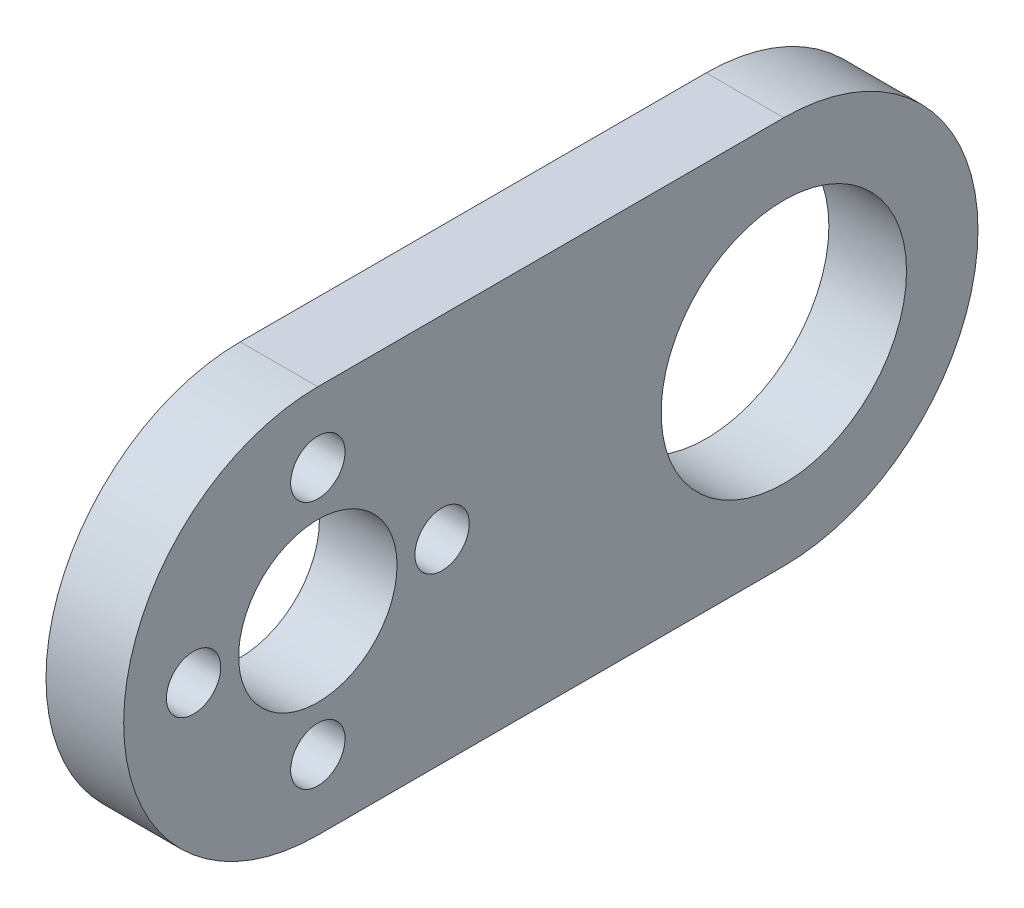
SolidWorks part; units mm, degrees
ref_plane "Alzado" through (0, 0, 0) normal (0, 0, 1) x (1, 0, 0)
ref_plane "Planta" through (0, 0, 0) normal (0, 1, 0) x (1, 0, 0)
ref_plane "Vista lateral" through (0, 0, 0) normal (1, 0, 0) x (0, 0, -1)
sketch "Croquis1" plane through (0, 0, 0) normal (1, 0, 0) x (0, 0, -1)
  line L0 (-27.5, 0) -> (27.5, 0) construction
  line L1 (-15, -12.5) -> (15, -12.5)
  line L2 (-15, 12.5) -> (-15, -12.5) construction
  line L3 (-15, 12.5) -> (15, 12.5)
  line L4 (15, 12.5) -> (15, -12.5) construction
  circle A0 centre (15, 0) radius 7.9
  circle A1 centre (-15, 0) radius 5.1
  arc A2 (15, 12.5) -> (15, -12.5) centre (15, 0) cw
  arc A3 (-15, -12.5) -> (-15, 12.5) centre (-15, 0) cw
  circle A4 centre (-23, 0) radius 1.75
  circle A5 centre (-15, 8) radius 1.75
  circle A6 centre (-7, 0) radius 1.75
  circle A7 centre (-15, -8) radius 1.75
  point P0 (0, 0)
  point P25 (-15, 0)
  dimension "D3" = 15.8
  dimension "D5" = 12.5
  dimension "D8" = 15
  dimension "D13" = 8
  dimension "D6" = 12.5
  dimension "D9" = 15
  dimension "D10" = 12.5
  dimension "D4" = 10.2
  dimension "D7" = 12.5
  dimension "D12" = 3.5
  dimension "D1" = 30
  dimension "D2" = 25
  dimension "D11" = 12.5
extrude "Saliente-Extruir1" add sketch "Croquis1" along normal blind 5
